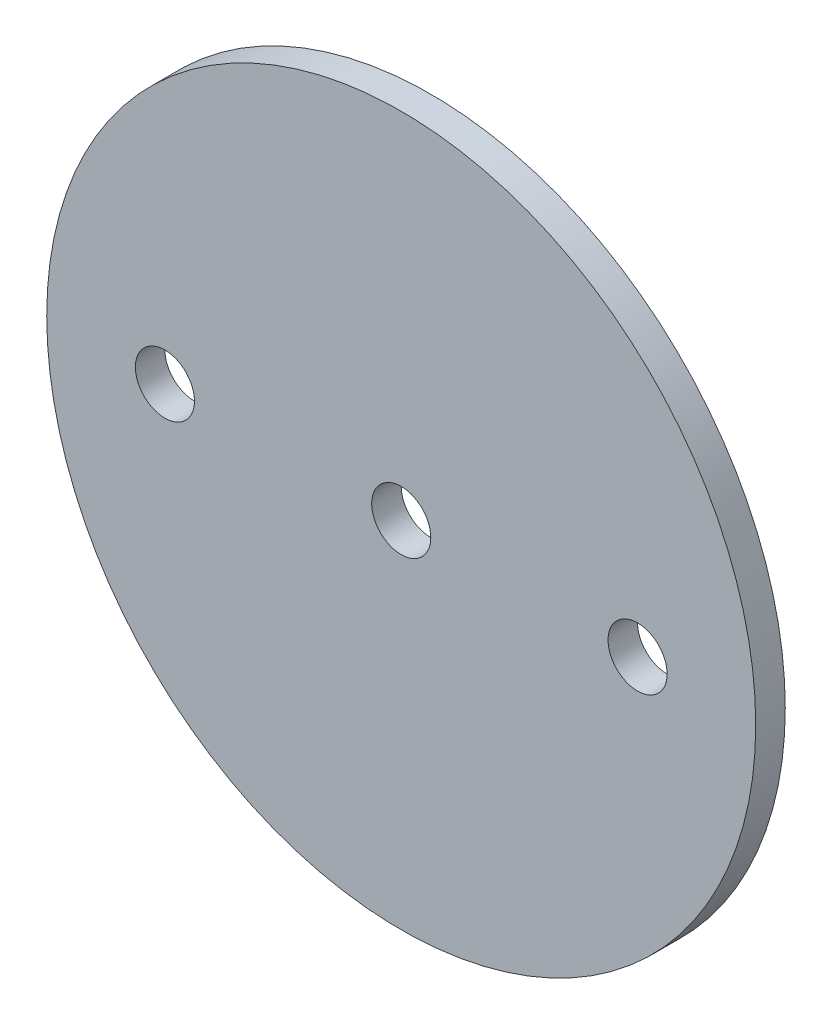
SolidWorks part; units mm, degrees
ref_plane "Front Plane" through (0, 0, 0) normal (0, 0, 1) x (1, 0, 0)
ref_plane "Top Plane" through (0, 0, 0) normal (0, 1, 0) x (1, 0, 0)
ref_plane "Right Plane" through (0, 0, 0) normal (1, 0, 0) x (0, 0, -1)
sketch "Sketch1" plane through (0, 0, 0) normal (0, 0, 1) x (1, 0, 0)
  circle A0 centre (0, 0) radius 38.1
extrude "Boss-Extrude1" add sketch "Sketch1" along normal mid plane 3.175
sketch "Sketch2" plane through (0, 0, 1.5875) normal (0, 0, 1) x (1, 0, 0)
  line L0 (-1000, 0) -> (49000, 0) construction
  point P1 (0, 0)
  point P4 (25.4, 0)
  point P5 (-25.4, 0)
  dimension "D1" = 25.4
  dimension "D2" = 50.8
hole_wizard "1/4 (0.25) Diameter Hole1" positions "Sketch2" profile "Sketch3" hole size "1/4" standard "ANSI Inch" end condition through all
sketch "Sketch3" plane through (-25.4, 0, 1.5875) normal (1, 0, 0) x (0, -1, 0)
  line L0 (0, 0) -> (0, 3.175)
  line L1 (0, 3.175) -> (3.175, 3.175)
  line L2 (3.175, 3.175) -> (3.175, 0)
  line L5 (3.175, 0) -> (0, 0)
  line L11 (0, -6.35) -> (0, 107.95) construction
  dimension "Thru Hole Dia." = 6.35
  dimension "Thru Hole Depth" = 3.175
equation "\"AIRFRAME_OD\"= 3.091in"
equation "\"AIRFRAME_ID\"= 3.00in"
equation "\"FLAT_T\"= 0.125in"
equation "\"NOSE_EXP_L\"= 3.5in"
equation "\"NOSE_SHOULDER_L\"= 5in"
equation "\"MAIN_L\"= 30in"
equation "\"RECO_COUP_L\"= 6in"
equation "\"RECO_SWITCH_L\"= 1.5in"
equation "\"DROGUE_L\"= 14in"
equation "\"ATS_FORE_COUP_L\"= 4in"
equation "\"ATS_AFT_COUP_L\"= 2.5in"
equation "\"LOWER_L\"= 16in"
equation "\"FIN_N\"= 4"
equation "\"CR_AFT_X\"= 0.5in"
equation "\"CR_FORE_X\"= 6in"
equation "\"FIN_ROOT\"= 5in"
equation "\"FIN_X\"= 0.75in"
equation "\"MOTOR_OD\"= 2.25in"
equation "\"MOTOR_ID\"= 2.126in"
equation "\"COUPLER_OD\"= 2.998in"
equation "\"COUPLER_ID\"= 2.875in"
equation "\"D1@Sketch1\"=\"AIRFRAME_ID\""
equation "\"D1@Boss-Extrude1\"=\"FLAT_T\""
equation "\"RECO_ROD_X\"= 1.5in"
equation "\"ATS_ROD_X\"= 2in"
equation "\"D1@Sketch2\"=\"ATS_ROD_X\"*0.5"
equation "\"D2@Sketch2\"=\"ATS_ROD_X\""
